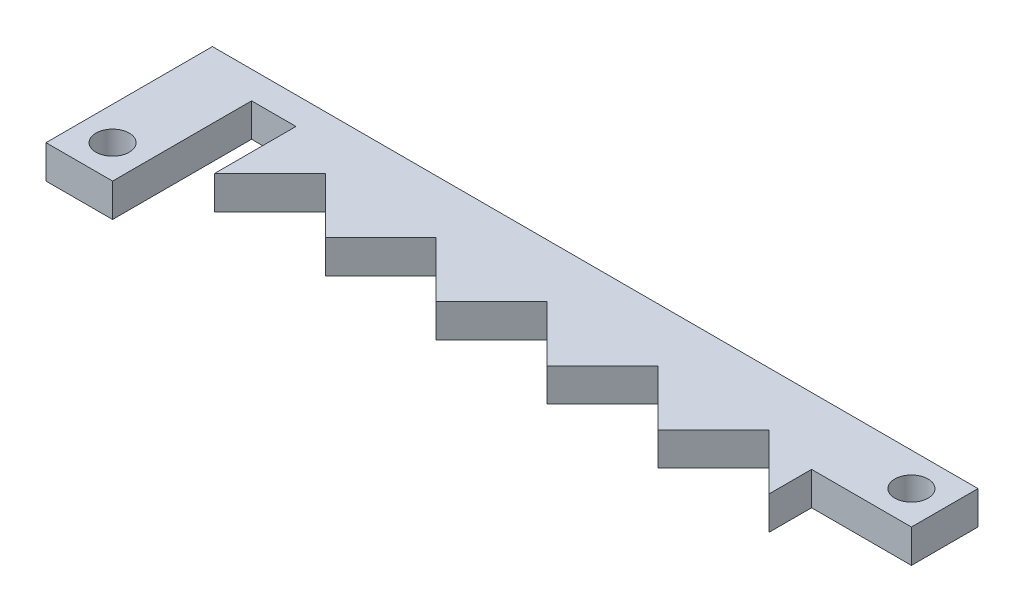
SolidWorks part; units mm, degrees
material "Custom Plastic"
ref_plane "Front Plane" through (0, 0, 0) normal (0, 0, 1) x (1, 0, 0)
ref_plane "Top Plane" through (0, 0, 0) normal (0, 1, 0) x (1, 0, 0)
ref_plane "Right Plane" through (0, 0, 0) normal (1, 0, 0) x (0, 0, -1)
sketch "Sketch1" plane through (0, 0, 0) normal (0, 1, 0) x (1, 0, 0)
  line L0 (0, 42.3412) -> (0, 38.3412)
  line L1 (0, 38.3412) -> (5, 43.3412)
  line L2 (5, 43.3412) -> (10, 38.3412)
  line L3 (10, 38.3412) -> (15, 43.3412)
  line L4 (15, 43.3412) -> (20, 38.3412)
  line L5 (20, 38.3412) -> (25, 43.3412)
  line L6 (25, 43.3412) -> (30, 38.3412)
  line L7 (30, 38.3412) -> (35, 43.3412)
  line L8 (35, 43.3412) -> (40, 38.3412)
  line L9 (40, 38.3412) -> (45, 43.3412)
  line L10 (45, 43.3412) -> (50, 38.3412)
  line L15 (5, 48.1688) -> (58.9437, 48.1688)
  line L16 (50, 42.1688) -> (50, 38.3412)
  line L20 (0, 42.3412) -> (0, 45.6968)
  line L26 (-1.8488, 48.1688) -> (-10, 48.1688)
  line L27 (5, 48.1688) -> (-1.8488, 48.1688)
  line L28 (-10, 48.1688) -> (-10, 33.1688)
  line L29 (-10, 33.1688) -> (-4, 33.1688)
  line L30 (-4, 33.1688) -> (-4, 45.6968)
  line L31 (-4, 45.6968) -> (0, 45.6968)
  line L32 (-10, 36.1688) -> (-4, 36.1688) construction
  line L33 (58.9437, 48.1688) -> (59, 48.1688)
  line L34 (59, 48.1688) -> (59, 42.1688)
  line L35 (59, 42.1688) -> (50, 42.1688)
  line L36 (56, 48.1688) -> (56, 42.1688) construction
  circle A2 centre (-7, 36.1688) radius 1.5
  circle A3 centre (56, 45.1688) radius 1.5
  dimension "D7" = 3
  dimension "D9" = 6
  dimension "D11" = 3
  dimension "D1" = 10
  dimension "D2" = 5
  dimension "D3" = 6
  dimension "D5" = 15
  dimension "D6" = 10
  dimension "D8" = 3
  dimension "D10" = 9
  dimension "D12" = 3
  dimension "D13" = 50
  dimension "D4" = 5
extrude "Boss-Extrude1" add sketch "Sketch1" along normal blind 3
